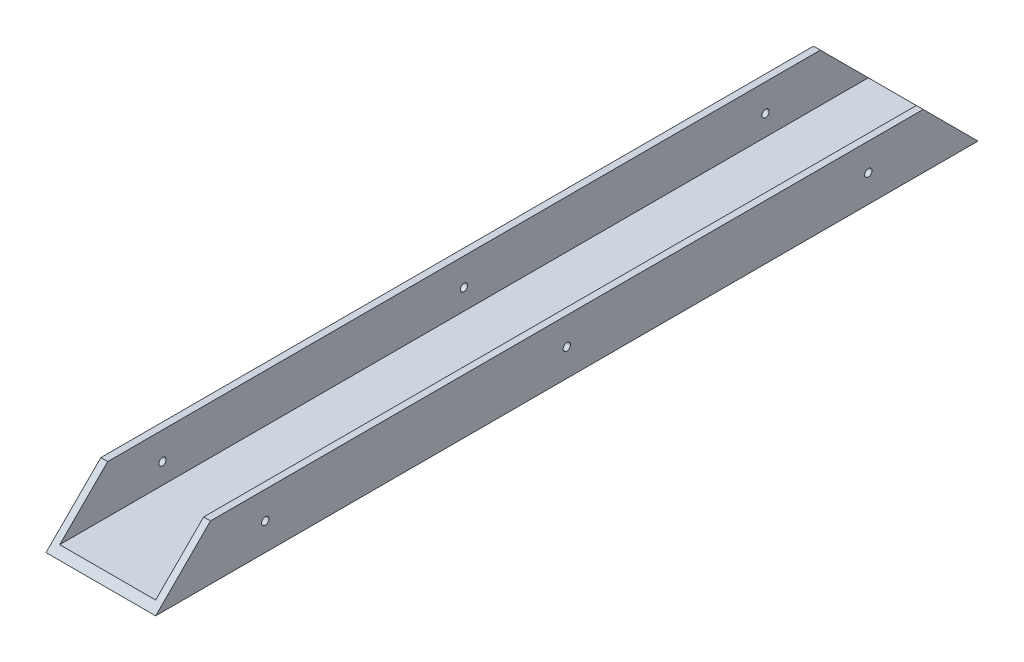
SolidWorks part; units mm, degrees
material "AISI 1010 Steel, hot rolled bar"
ref_plane "Front Plane" through (0, 0, 0) normal (0, 0, 1) x (1, 0, 0)
ref_plane "Top Plane" through (0, 0, 0) normal (0, 1, 0) x (1, 0, 0)
ref_plane "Right Plane" through (0, 0, 0) normal (1, 0, 0) x (0, 0, -1)
sketch "Sketch1" plane through (0, 0, 0) normal (0, 0, 1) x (1, 0, 0)
  line L0 (-25.4, 0) -> (25.4, 0)
  line L1 (25.4, 0) -> (25.4, 25.4)
  line L2 (25.4, 25.4) -> (22.225, 25.4)
  line L3 (22.225, 25.4) -> (22.225, 3.175)
  line L4 (22.225, 3.175) -> (-22.225, 3.175)
  line L5 (-22.225, 3.175) -> (-22.225, 25.4)
  line L6 (-22.225, 25.4) -> (-25.4, 25.4)
  line L7 (-25.4, 25.4) -> (-25.4, 0)
  line L8 (0, 15.5567) -> (0, -9.8218) construction
  dimension "D1" = 3.175
  dimension "D2" = 3.175
  dimension "D3" = 25.4
  dimension "D4" = 50.8
extrude "Boss-Extrude1" add sketch "Sketch1" along normal blind 381
sketch "Sketch2" plane through (25.4, 0, 0) normal (1, 0, 0) x (0, 0, -1)
  line L0 (-381, 0) -> (-355.6, 25.4)
  line L1 (-381, 25.4) -> (0, 25.4) construction
  line L2 (-355.6, 25.4) -> (-381, 25.4)
  line L3 (-381, 25.4) -> (-381, 0)
  line L4 (0, 0) -> (0, 25.4)
  line L5 (0, 25.4) -> (-25.4, 25.4)
  line L6 (-25.4, 25.4) -> (0, 0)
  dimension "D1" = 45
  dimension "D2" = 45
extrude "Cut-Extrude1" cut sketch "Sketch2" against normal through all
sketch "Sketch3" [suppressed] plane through (0, 0, 0) normal (0, -1, 0) x (1, 0, 0)
  line L0 (0, 304.8) -> (0, 0) construction
  line L1 (-25.4, 304.8) -> (25.4, 304.8) construction
  line L2 (-25.4, 0) -> (25.4, 0) construction
  circle A0 centre (0, 254) radius 2.5
  circle A1 centre (0, 76.2) radius 2.5
  dimension "D3" = 19.05
  dimension "D1" = 177.8
  dimension "D2" = 76.2
extrude "Cut-Extrude2" [suppressed] cut sketch "Sketch3" against normal blind 330.2
sketch "Sketch4" [suppressed] plane through (0, 0, 0) normal (0, -1, 0) x (1, 0, 0)
  line L0 (0, 381) -> (0, 0) construction
  line L1 (-25.4, 381) -> (25.4, 381) construction
  line L2 (-25.4, 190.5) -> (25.4, 190.5) construction
  line L3 (-13.97, 276.86) -> (13.97, 276.86)
  line L4 (-20.32, 276.86) -> (-20.32, 304.8)
  line L5 (-13.97, 304.8) -> (13.97, 304.8)
  line L6 (20.32, 276.86) -> (20.32, 304.8)
  line L7 (-20.32, 276.86) -> (20.32, 304.8) construction
  line L8 (-20.32, 304.8) -> (20.32, 276.86) construction
  line L9 (-25.4, 381) -> (-25.4, 0) construction
  line L10 (25.4, 381) -> (25.4, 0) construction
  line L11 (-20.32, 104.14) -> (-20.32, 76.2)
  line L12 (-13.97, 104.14) -> (13.97, 104.14)
  line L17 (-25.4, 290.83) -> (25.4, 290.83) construction
  line L18 (20.32, 104.14) -> (20.32, 76.2)
  line L19 (-13.97, 76.2) -> (13.97, 76.2)
  arc A0 (-13.97, 304.8) -> (-20.32, 304.8) centre (-17.145, 304.8) ccw
  arc A1 (13.97, 304.8) -> (20.32, 304.8) centre (17.145, 304.8) cw
  arc A2 (13.97, 276.86) -> (20.32, 276.86) centre (17.145, 276.86) ccw
  arc A3 (-13.97, 276.86) -> (-20.32, 276.86) centre (-17.145, 276.86) cw
  arc A4 (-13.97, 76.2) -> (-20.32, 76.2) centre (-17.145, 76.2) cw
  arc A5 (-13.97, 104.14) -> (-20.32, 104.14) centre (-17.145, 104.14) ccw
  arc A6 (13.97, 104.14) -> (20.32, 104.14) centre (17.145, 104.14) cw
  arc A7 (13.97, 76.2) -> (20.32, 76.2) centre (17.145, 76.2) ccw
  point P5 (0, 290.83)
  dimension "D4" = 6.35
  dimension "D1" = 27.94
  dimension "D2" = 40.64
  dimension "D3" = 76.2
extrude "Cut-Extrude3" [suppressed] cut sketch "Sketch4" against normal through all
sketch "Sketch5" plane through (-25.4, 0, 0) normal (-1, 0, 0) x (0, 0, 1)
  line L0 (12.7, 12.7) -> (368.3, 12.7) construction
  line L1 (25.4, 25.4) -> (0, 0) construction
  line L2 (381, 0) -> (355.6, 25.4) construction
  line L3 (190.5, 12.7) -> (190.5, 25.4) construction
  line L4 (355.6, 25.4) -> (25.4, 25.4) construction
  line L5 (0, 0) -> (0, 25.4) construction
  point P10 (50.8, 12.7)
  point P11 (330.2, 12.7)
  dimension "D1" = 50.8
hole_wizard "M3 Clearance Hole1" positions "3DSketch1" profile "Sketch6" hole size "M3" standard "ANSI Metric" end condition through all
sketch3d "3DSketch1"
  point P0 (-25.4, 12.7, 50.8)
  point P3 (-25.4, 12.7, 190.5)
  point P6 (-25.4, 12.7, 330.2)
sketch "Sketch6" plane through (-25.4, 12.7, 50.8) normal (0, 1, 0) x (0, 0, 1)
  line L0 (0, 0) -> (0, 50.8)
  line L1 (0, 50.8) -> (1.7, 50.8)
  line L2 (1.7, 50.8) -> (1.7, 0)
  line L5 (1.7, 0) -> (0, 0)
  line L11 (0, -6.35) -> (0, 107.95) construction
  dimension "Thru Hole Dia." = 3.4
  dimension "Thru Hole Depth" = 50.8
equation "\"D2@Sketch1\"=\"D1@Sketch1\""
